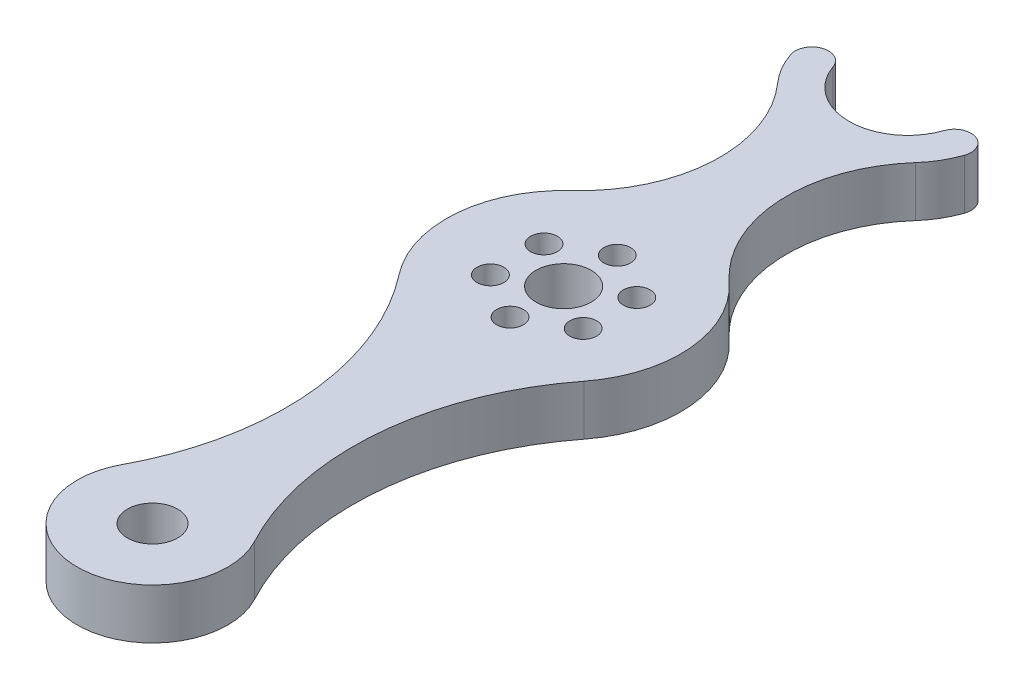
SolidWorks part; units mm, degrees
ref_plane "Front Plane" through (0, 0, 0) normal (0, 0, 1) x (1, 0, 0)
ref_plane "Top Plane" through (0, 0, 0) normal (0, 1, 0) x (1, 0, 0)
ref_plane "Right Plane" through (0, 0, 0) normal (1, 0, 0) x (0, 0, -1)
sketch "Sketch1" plane through (0, 0, 0) normal (0, 1, 0) x (1, 0, 0)
  line L0 (0, -52.0078) -> (0, -44.0078) construction
  circle A0 centre (0, -68.5564) radius 4 construction
  circle A1 centre (0, -68.5564) radius 4 construction
  arc A2 (-4.7216, -63.3885) -> (4.7216, -63.3885) centre (0, -68.5564) ccw
  circle A3 centre (0, -68.5564) radius 7 construction
  circle A4 centre (0, -48.0078) radius 4 construction
  circle A5 centre (0, -68.5564) radius 16.5485 construction
  circle A7 centre (0, -48.0078) radius 3.5 construction
  circle A14 centre (0, -68.5564) radius 1.65 construction
  circle A15 centre (0, -68.5564) radius 1.65
  arc A16 (-5.1989, -49.8026) -> (-4.1113, -51.6613) centre (0, -48.0078) ccw
  arc A17 (-4.1113, -51.6613) -> (-4.7216, -63.3885) centre (-10.3616, -57.2155) cw
  arc A18 (4.1113, -51.6613) -> (4.7216, -63.3885) centre (10.3616, -57.2155) ccw
  arc A19 (5.1989, -49.8026) -> (4.1113, -51.6613) centre (0, -48.0078) cw
  arc A20 (-3.3084, -49.1499) -> (3.3084, -49.1499) centre (0, -48.0078) ccw
  arc A21 (-5.1989, -49.8026) -> (-3.3084, -49.1499) centre (-4.2537, -49.4762) cw
  arc A22 (5.1989, -49.8026) -> (3.3084, -49.1499) centre (4.2537, -49.4762) ccw
  circle A23 centre (0, -68.5564) radius 20.5485 construction
  point P37 (-2, -57.2155)
  point P38 (2, -57.2155)
  dimension "D2" = 1
  dimension "D4" = 4
  dimension "D1" = 0.5
extrude "Boss-Extrude1" add sketch "Sketch1" along normal blind 3
sketch "Sketch2" plane through (0, 0, 0) normal (0, -1, 0) x (1, 0, 0)
  line L0 (0, 52.0078) -> (0, 44.0078) construction
  circle A0 centre (0, 93.1049) radius 1.5
  circle A1 centre (-22.8961, 45.1123) radius 1.5 construction
  arc A2 (-3.9694, 90.985) -> (3.9694, 90.985) centre (0, 93.1049) cw
  arc A3 (-3.9694, 90.985) -> (-5.5233, 72.8568) centre (-18.7014, 83.1171) cw
  arc A4 (4.7216, 63.3885) -> (-4.7216, 63.3885) centre (0, 68.5564) ccw construction
  arc A5 (3.9694, 90.985) -> (5.5233, 72.8568) centre (18.7014, 83.1171) ccw
  arc A6 (-5.5233, 72.8568) -> (5.5233, 72.8568) centre (0, 68.5564) cw
  circle A7 centre (0, 68.5564) radius 24.5485 construction
  point P5 (0, 94.6049)
  point P6 (0, 97.6049)
  point P14 (-2, 83.1171)
  point P17 (2, 83.1171)
  dimension "D2" = 3
extrude "Boss-Extrude2" add sketch "Sketch2" against normal up to surface (3 mm away) up to face at (0, 3, 55.1247)
sketch "Sketch3" plane through (0, 3, 0) normal (0, 1, 0) x (1, 0, 0)
  circle A0 centre (0, -65.3564) radius 0.8
  circle A1 centre (0, -68.5564) radius 4 construction
  circle A2 centre (2.7713, -66.9564) radius 0.8
  circle A3 centre (2.7713, -70.1564) radius 0.8
  circle A4 centre (0, -71.7564) radius 0.8
  circle A5 centre (-2.7713, -70.1564) radius 0.8
  circle A6 centre (-2.7713, -66.9564) radius 0.8
  point P17 (0, -68.5564)
  dimension "D1" = 1.6
  dimension "D2" = 6
extrude "Cut-Extrude1" cut sketch "Sketch3" against normal through all
ref_axis "Axis1" through (0, 3, 93.1049) along (0, -1, 0)
